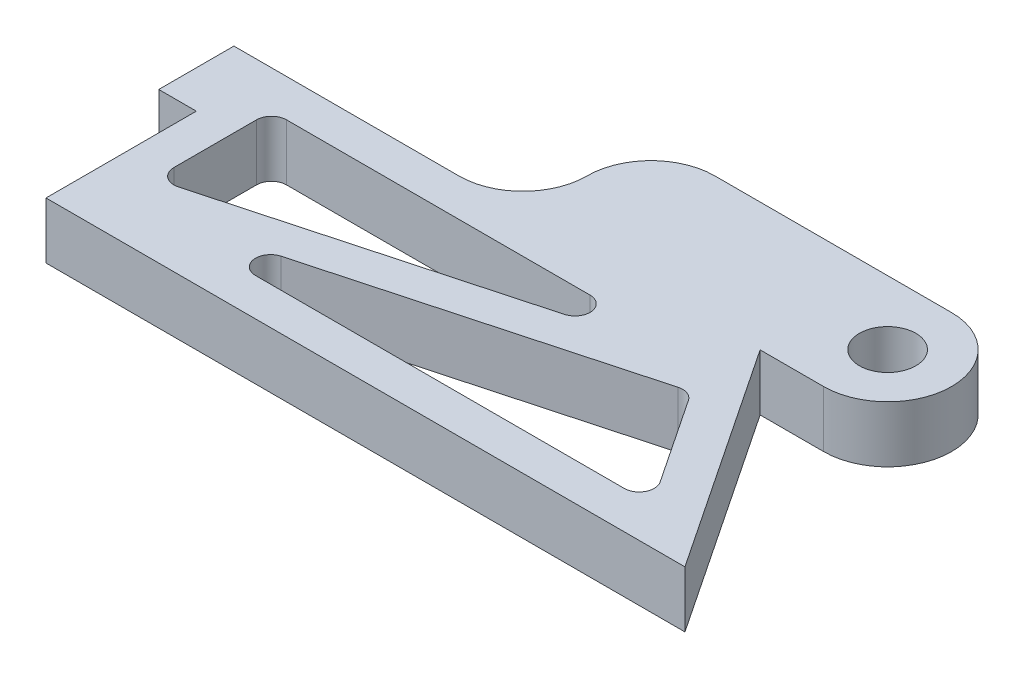
SolidWorks part; units mm, degrees
material "UHMW"
ref_plane "Front Plane" through (0, 0, 0) normal (0, 0, 1) x (1, 0, 0)
ref_plane "Top Plane" through (0, 0, 0) normal (0, 1, 0) x (1, 0, 0)
ref_plane "Right Plane" through (0, 0, 0) normal (1, 0, 0) x (0, 0, -1)
other "Bounding Box"
ref_plane "Default Plane" through (-8.9266, -12.7485, 0) normal (-0.1736, 0.9848, 0) x (0.9848, 0.1736, 0)
sketch "Sketch1" plane through (0, 0, 0) normal (0, 1, 0) x (1, 0, 0)
  line L0 (0, 0) -> (38.0339, 0)
  line L1 (88.9, 0) -> (114.3, -38.1)
  line L2 (114.3, -38.1) -> (6.35, -38.1)
  line L3 (6.35, -38.1) -> (6.35, -12.7)
  line L4 (6.35, -12.7) -> (0, -12.7)
  line L5 (0, -12.7) -> (0, 0)
  line L6 (99.6289, 0) -> (88.9, 0)
  line L7 (48.8289, 10.837) -> (48.8289, 10.795)
  line L9 (99.6289, 21.632) -> (59.6239, 21.632)
  line L13 (89.2149, -11.9199) -> (102.4349, -31.75)
  line L14 (102.4349, -31.75) -> (16.4133, -31.75)
  line L15 (12.7, -26.1801) -> (12.7, -6.35)
  line L16 (12.7, -6.35) -> (85.5016, -6.35)
  line L17 (12.7, -26.1801) -> (85.5016, -6.35)
  line L18 (89.2149, -11.9199) -> (16.4133, -31.75)
  circle A0 centre (99.6289, 10.816) radius 4.7625
  arc A1 (99.6289, 21.632) -> (99.6289, 0) centre (99.6289, 10.816) cw
  arc A2 (59.6239, 21.632) -> (48.8289, 10.837) centre (59.6239, 10.837) ccw
  arc A3 (48.8289, 10.795) -> (38.0339, 0) centre (38.0339, 10.795) cw
  point P16 (48.8289, 0)
  point P26 (15.343, -5.9749)
  point P27 (80.4949, -4.4473)
  dimension "D7" = 50.8
  dimension "D8" = 9.525
  dimension "D9" = 10.7289
  dimension "D6" = 10.816
  dimension "D10" = 10.795
  dimension "D1" = 6.35
  dimension "D2" = 38.1
  dimension "D3" = 107.95
  dimension "D4" = 88.9
  dimension "D5" = 12.7
  dimension "D11" = 6.35
  dimension "D12" = 6.35
  dimension "D13" = 6.35
  dimension "D14" = 6.35
  dimension "D15" = 6.35
extrude "Boss-Extrude1" add sketch "Sketch1" along normal blind 9.525
fillet "Fillet6" radius 2.54 6 edges at (102.4349, 4.7625, 31.75) (89.2149, 4.7625, 11.9199) (16.4133, 4.7625, 31.75) (12.7, 4.7625, 26.1801) (12.7, 4.7625, 6.35) (85.5016, 4.7625, 6.35)
